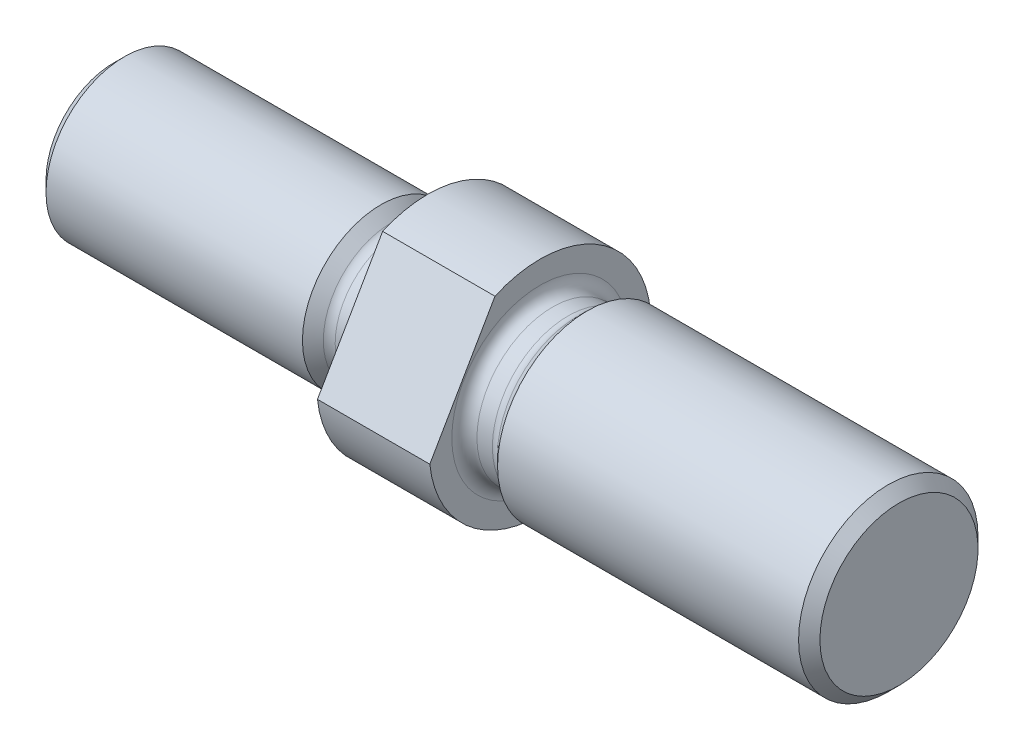
SolidWorks part; units mm, degrees
ref_plane "Front Plane" through (0, 0, 0) normal (0, 0, 1) x (1, 0, 0)
ref_plane "Top Plane" through (0, 0, 0) normal (0, 1, 0) x (1, 0, 0)
ref_plane "Right Plane" through (0, 0, 0) normal (1, 0, 0) x (0, 0, -1)
sketch "Sketch1" plane through (0, 0, 0) normal (0, 0, 1) x (1, 0, 0)
  line L0 (0, 0) -> (0, 4.7942)
  line L1 (0, 4.7942) -> (0.762, 5.5563)
  line L2 (0.762, 5.5563) -> (18.9124, 5.5563)
  line L3 (18.9124, 5.5563) -> (19.6511, 4.8175)
  line L4 (20.2438, 4.572) -> (21.3868, 4.572)
  line L5 (22.225, 5.4102) -> (22.225, 7.8486)
  line L6 (22.225, 7.8486) -> (30.1752, 7.8486)
  line L7 (30.1752, 7.8486) -> (30.1752, 0)
  line L8 (30.1752, 0) -> (0, 0)
  line L9 (30.1752, 0) -> (0, 0) construction
  arc A0 (19.6511, 4.8175) -> (20.2438, 4.572) centre (20.2438, 5.4102) ccw
  arc A1 (21.3868, 4.572) -> (22.225, 5.4102) centre (21.3868, 5.4102) ccw
revolve "Revolve1" add sketch "Sketch1" angle 360 about L9 reverse direction yes
cosmetic thread "Cosmetic Thread1" parameters "D1"=19.6511, "D2"=9.6012
sketch "Sketch2" plane through (0, 0, 0) normal (1, 0, 0) x (0, 0, -1)
  line L0 (-21.8591, -5.8571) -> (5.8571, -21.8591)
  line L1 (5.8571, -21.8591) -> (21.8591, 5.8571)
  line L2 (21.8591, 5.8571) -> (-5.8571, 21.8591)
  line L3 (-5.8571, 21.8591) -> (-21.8591, -5.8571)
  line L4 (2.2272, -8.8424) -> (8.7714, 2.4924)
  line L5 (-2.2272, 8.8424) -> (-8.7714, -2.4924)
  arc A0 (-8.7714, -2.4924) -> (2.2272, -8.8424) centre (0, 0) ccw
  arc A1 (8.7714, 2.4924) -> (-2.2272, 8.8424) centre (0, 0) ccw
sketch "Sketch3" plane through (0, 0, 0) normal (0, 0, 1) x (1, 0, 0)
  line L0 (30.1752, 0) -> (30.1752, 6.2484)
  line L1 (31.0642, 5.3594) -> (32.1564, 5.3594)
  line L2 (32.785, 5.6198) -> (33.5152, 6.35)
  line L3 (33.5152, 6.35) -> (54.8195, 6.35)
  line L4 (54.8195, 6.35) -> (55.5752, 5.5944)
  line L5 (55.5752, 5.5944) -> (55.5752, 0)
  line L6 (55.5752, 0) -> (30.1752, 0)
  line L7 (55.5752, 0) -> (30.1752, 0) construction
  arc A0 (30.1752, 6.2484) -> (31.0642, 5.3594) centre (31.0642, 6.2484) ccw
  arc A1 (32.1564, 5.3594) -> (32.785, 5.6198) centre (32.1564, 6.2484) ccw
revolve "Revolve2" add sketch "Sketch3" angle 360 about L7 reverse direction yes
cosmetic thread "Cosmetic Thread2" parameters "D1"=22.7902, "D2"=11.1887
extrude "Cut-Extrude1" cut sketch "Sketch2" along normal blind 31.4452
ref_plane "Plane1" through (20.5232, 0, 0) normal (1, 0, 0) x (0, 0, -1)
ref_plane "Plane2" through (22.225, 0, 0) normal (1, 0, 0) x (0, 0, -1)
ref_plane "Plane3" through (0, 0, 0) normal (0, 0, 1) x (1, 0, 0)
ref_plane "Plane4" through (55.5752, 0, 0) normal (1, 0, 0) x (0, 0, -1)
ref_plane "Plane5" through (63.4492, 0, 0) normal (1, 0, 0) x (0, 0, -1)
ref_plane "Plane6" through (30.1752, 0, 0) normal (1, 0, 0) x (0, 0, -1)
ref_plane "b11 XY" through (0, 0, 0) normal (0, 0, 1) x (1, 0, 0)
ref_plane "b11 XZ" through (0, 6.35, 0) normal (0, -1, 0) x (-1, 0, 0)
ref_plane "b11 YZ" through (55.5752, 0, 0) normal (1, 0, 0) x (0, 0, -1)
ref_axis "b11 X" through (-80.9, 6.35, 0) along (1, 0, 0)
ref_axis "b11 Y" through (55.5752, -50, 0) along (0, 1, 0)
ref_axis "b11 Z" through (55.5752, 6.35, 80.9) along (0, 0, -1)
sketch3d "b11"
  point P0 (55.5752, 6.35, 0)
ref_plane "b22 XY" through (0, 0, 0) normal (0, 0, 1) x (1, 0, 0)
ref_plane "b22 XZ" through (0, -6.35, 0) normal (0, -1, 0) x (-1, 0, 0)
ref_plane "b22 YZ" through (55.5752, 0, 0) normal (1, 0, 0) x (0, 0, -1)
ref_axis "b22 X" through (-80.9, -6.35, 0) along (1, 0, 0)
ref_axis "b22 Y" through (55.5752, -50, 0) along (0, 1, 0)
ref_axis "b22 Z" through (55.5752, -6.35, 80.9) along (0, 0, -1)
sketch3d "b22"
  point P0 (55.5752, -6.35, 0)
ref_plane "c11 XY" through (0, 0, 0) normal (0, 0, 1) x (1, 0, 0)
ref_plane "c11 XZ" through (0, 0, 0) normal (0, -1, 0) x (-1, 0, 0)
ref_plane "c11 YZ" through (55.5752, 0, 0) normal (1, 0, 0) x (0, 0, -1)
ref_axis "c11 X" through (-80.9, 0, 0) along (1, 0, 0)
ref_axis "c11 Y" through (55.5752, -50, 0) along (0, 1, 0)
ref_axis "c11 Z" through (55.5752, 0, 80.9) along (0, 0, -1)
sketch3d "c11"
  point P0 (55.5752, 0, 0)
ref_plane "c22 XY" through (0, 0, 0) normal (0, 0, 1) x (1, 0, 0)
ref_plane "c22 XZ" through (0, 0, 0) normal (0, -1, 0) x (-1, 0, 0)
ref_plane "c22 YZ" through (30.1752, 0, 0) normal (1, 0, 0) x (0, 0, -1)
ref_axis "c22 X" through (-80.9, 0, 0) along (1, 0, 0)
ref_axis "c22 Y" through (30.1752, -50, 0) along (0, 1, 0)
ref_axis "c22 Z" through (30.1752, 0, 80.9) along (0, 0, -1)
sketch3d "c22"
  point P0 (30.1752, 0, 0)
ref_plane "g1 XY" through (0, 0, 0) normal (0, 0, 1) x (1, 0, 0)
ref_plane "g1 XZ" through (0, 0, 0) normal (0, -1, 0) x (-1, 0, 0)
ref_plane "g1 YZ" through (30.1752, 0, 0) normal (1, 0, 0) x (0, 0, -1)
ref_axis "g1 X" through (-80.9, 0, 0) along (1, 0, 0)
ref_axis "g1 Y" through (30.1752, -50, 0) along (0, 1, 0)
ref_axis "g1 Z" through (30.1752, 0, 80.9) along (0, 0, -1)
sketch3d "g1"
  point P0 (30.1752, 0, 0)
ref_plane "i1 XY" through (0, 0, 0) normal (0, 0, 1) x (1, 0, 0)
ref_plane "i1 XZ" through (0, 7.8486, 0) normal (0, -1, 0) x (-1, 0, 0)
ref_plane "i1 YZ" through (30.1752, 0, 0) normal (1, 0, 0) x (0, 0, -1)
ref_axis "i1 X" through (-80.9, 7.8486, 0) along (1, 0, 0)
ref_axis "i1 Y" through (30.1752, -50, 0) along (0, 1, 0)
ref_axis "i1 Z" through (30.1752, 7.8486, 80.9) along (0, 0, -1)
sketch3d "i1"
  point P0 (30.1752, 7.8486, 0)
ref_plane "i2 XY" through (0, 0, 0) normal (0, 0, 1) x (1, 0, 0)
ref_plane "i2 XZ" through (0, -7.8486, 0) normal (0, -1, 0) x (-1, 0, 0)
ref_plane "i2 YZ" through (30.1752, 0, 0) normal (1, 0, 0) x (0, 0, -1)
ref_axis "i2 X" through (-80.9, -7.8486, 0) along (1, 0, 0)
ref_axis "i2 Y" through (30.1752, -50, 0) along (0, 1, 0)
ref_axis "i2 Z" through (30.1752, -7.8486, 80.9) along (0, 0, -1)
sketch3d "i2"
  point P0 (30.1752, -7.8486, 0)
ref_plane "j1 XY" through (0, 0, 0) normal (1, 0, 0) x (0, 0, -1)
ref_plane "j1 XZ" through (0, 3.175, 0) normal (0, -1, 0) x (-1, 0, 0)
ref_plane "j1 YZ" through (0, 0, 5.4993) normal (0, 0, -1) x (-1, 0, 0)
ref_axis "j1 X" through (0, 3.175, 80.9) along (0, 0, -1)
ref_axis "j1 Y" through (0, -50, 5.4993) along (0, 1, 0)
ref_axis "j1 Z" through (80.9, 3.175, 5.4993) along (-1, 0, 0)
sketch3d "j1"
  point P0 (0, 3.175, 5.4993)
ref_plane "j2 XY" through (0, 0, 0) normal (1, 0, 0) x (0, 0, -1)
ref_plane "j2 XZ" through (0, -3.175, 0) normal (0, -1, 0) x (-1, 0, 0)
ref_plane "j2 YZ" through (0, 0, -5.4993) normal (0, 0, -1) x (-1, 0, 0)
ref_axis "j2 X" through (0, -3.175, 80.9) along (0, 0, -1)
ref_axis "j2 Y" through (0, -50, -5.4993) along (0, 1, 0)
ref_axis "j2 Z" through (80.9, -3.175, -5.4993) along (-1, 0, 0)
sketch3d "j2"
  point P0 (0, -3.175, -5.4993)
ref_plane "stud XY" through (55.5752, 0, 0) normal (-1, 0, 0) x (0, 0, 1)
ref_plane "stud XZ" through (0, 0, 0) normal (0, 1, 0) x (1, 0, 0)
ref_plane "stud YZ" through (0, 0, 0) normal (0, 0, -1) x (-1, 0, 0)
ref_axis "stud X" through (55.5752, 0, 80.9) along (0, 0, -1)
ref_axis "stud Y" through (55.5752, 50, 0) along (0, -1, 0)
ref_axis "stud Z" through (-80.9, 0, 0) along (1, 0, 0)
sketch3d "stud"
  point P0 (55.5752, 0, 0)
ref_plane "stud_re XY" through (63.4492, 0, 0) normal (-1, 0, 0) x (0, 0, 1)
ref_plane "stud_re XZ" through (0, 0, 0) normal (0, 1, 0) x (1, 0, 0)
ref_plane "stud_re YZ" through (0, 0, 0) normal (0, 0, -1) x (-1, 0, 0)
ref_axis "stud_re X" through (63.4492, 0, 80.9) along (0, 0, -1)
ref_axis "stud_re Y" through (63.4492, 50, 0) along (0, -1, 0)
ref_axis "stud_re Z" through (-80.9, 0, 0) along (1, 0, 0)
sketch3d "stud_re"
  point P0 (63.4492, 0, 0)
ref_plane "to_re XY" through (30.1752, 0, 0) normal (-1, 0, 0) x (0, 0, 1)
ref_plane "to_re XZ" through (0, 0, 0) normal (0, 1, 0) x (1, 0, 0)
ref_plane "to_re YZ" through (0, 0, 0) normal (0, 0, -1) x (-1, 0, 0)
ref_axis "to_re X" through (30.1752, 0, 80.9) along (0, 0, -1)
ref_axis "to_re Y" through (30.1752, 50, 0) along (0, -1, 0)
ref_axis "to_re Z" through (-80.9, 0, 0) along (1, 0, 0)
sketch3d "to_re"
  point P0 (30.1752, 0, 0)
ref_plane "to_rod XY" through (20.5232, 0, 0) normal (1, 0, 0) x (0, 0, -1)
ref_plane "to_rod XZ" through (0, 0, 0) normal (0, -1, 0) x (-1, 0, 0)
ref_plane "to_rod YZ" through (0, 0, 0) normal (0, 0, -1) x (-1, 0, 0)
ref_axis "to_rod X" through (20.5232, 0, 80.9) along (0, 0, -1)
ref_axis "to_rod Y" through (20.5232, -50, 0) along (0, 1, 0)
ref_axis "to_rod Z" through (80.9, 0, 0) along (-1, 0, 0)
sketch3d "to_rod"
  point P0 (20.5232, 0, 0)
